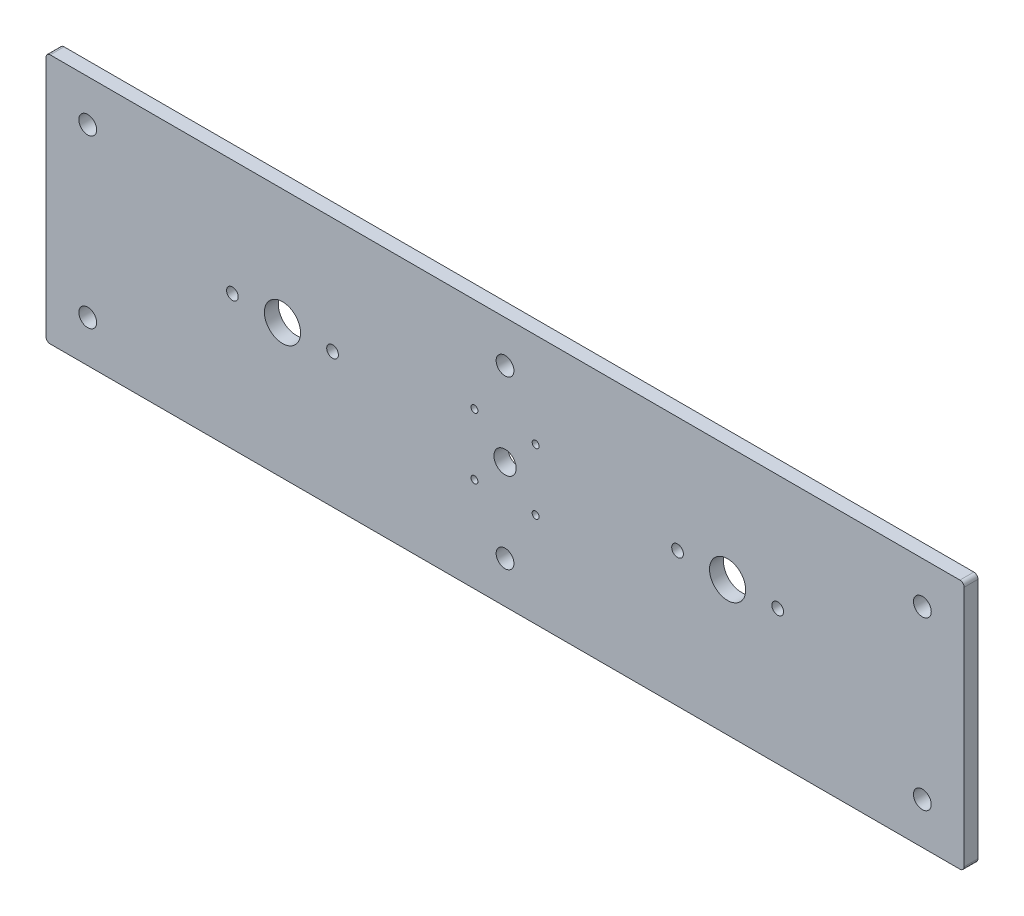
SolidWorks part; units mm, degrees
ref_plane "Front Plane" through (0, 0, 0) normal (0, 0, 1) x (1, 0, 0)
ref_plane "Top Plane" through (0, 0, 0) normal (0, 1, 0) x (1, 0, 0)
ref_plane "Right Plane" through (0, 0, 0) normal (1, 0, 0) x (0, 0, -1)
sketch "Sketch1" plane through (0, 0, 0) normal (0, 0, 1) x (1, 0, 0)
  line L1 (-165, -45) -> (165, -45)
  line L2 (-165, -45) -> (-165, 45)
  line L3 (-165, 45) -> (165, 45)
  line L4 (165, -45) -> (165, 45)
  line L5 (-165, -45) -> (165, 45) construction
  line L6 (-165, 45) -> (165, -45) construction
  point P0 (0, 0)
  dimension "D1" = 330
  dimension "D2" = 90
extrude "Boss-Extrude1" add sketch "Sketch1" along normal mid plane 5
hole_wizard "M6 Clearance Hole1" positions "Sketch6" profile "Sketch5" hole size "M6" standard "ANSI Metric"
sketch "Sketch6" plane through (0, 0, 2.5) normal (0, 0, 1) x (1, 0, 0)
  line L0 (-999.1588, 30) -> (49000.8412, 30) construction
  line L1 (-996.5045, -30) -> (49003.4955, -30) construction
  line L2 (-150, -995.3212) -> (-150, 49004.6788) construction
  line L3 (0, -1000) -> (0, 49000) construction
  line L4 (150, -1006.2702) -> (150, 48993.7298) construction
  line L5 (-165, 45) -> (-165, -45) construction
  line L6 (165, -45) -> (165, 45) construction
  line L7 (165, 45) -> (-165, 45) construction
  line L8 (-165, -45) -> (165, -45) construction
  point P27 (-150, 30)
  point P29 (-150, -30)
  point P31 (0, 30)
  point P33 (0, -30)
  point P35 (150, -30)
  point P37 (150, 30)
  dimension "D1" = 15
  dimension "D2" = 15
  dimension "D3" = 15
  dimension "D4" = 15
sketch "Sketch5" plane through (-150, 30, 2.5) normal (1, 0, 0) x (0, -1, 0)
  line L0 (0, 0) -> (0, 11.9228)
  line L1 (0, 11.9228) -> (3.2, 10)
  line L2 (3.2, 10) -> (3.2, 0)
  line L5 (3.2, 0) -> (0, 0)
  line L10 (0, 11.9228) -> (-3.2, 10) construction
  line L11 (0, -6.35) -> (0, 107.95) construction
  dimension "Hole Dia." = 6.4
  dimension "Hole Depth" = 10
  dimension "Drill Angle" = 118
sketch "Sketch3" plane through (0, 0, 2.5) normal (0, 0, 1) x (1, 0, 0)
  line L0 (-165, 3.4) -> (165, 3.4) construction
  circle A0 centre (-80, 3.4) radius 6.5
  dimension "D1" = 13
  dimension "D7" = 80
  dimension "D3" = 3.4
extrude "Cut-Extrude2" cut sketch "Sketch3" against normal through all
hole_wizard "M5x0.8 Tapped Hole1" positions "Sketch8" profile "Sketch7" tap size "M5x0.8" standard "ANSI Metric" end condition through all
sketch "Sketch8" plane through (0, 0, 2.5) normal (0, 0, 1) x (1, 0, 0)
  line L0 (-1080, 3.4) -> (48920, 3.4) construction
  circle A0 centre (-80, 3.4) radius 6.5 construction
  point P6 (-98, 3.4)
  point P8 (-62, 3.4)
  dimension "D1" = 18
  dimension "D2" = 18
sketch "Sketch7" plane through (-98, 3.4, 2.5) normal (1, 0, 0) x (0, -1, 0)
  line L0 (0, 0) -> (0, 5)
  line L1 (0, 5) -> (2.1, 5)
  line L2 (2.1, 5) -> (2.1, 0)
  line L5 (2.1, 0) -> (0, 0)
  line L11 (0, -6.35) -> (0, 107.95) construction
  dimension "Thru Tap Drill Dia." = 4.2
  dimension "Thru Tap Drill Depth" = 5
cosmetic thread "Hole Thread1" parameters "D2"=5
cosmetic thread "Hole Thread2" parameters "D2"=5
mirror "Mirror1" about plane through (0, 0, 0) normal (1, 0, 0) of "M5x0.8 Tapped Hole1", "Cut-Extrude2"
sketch "Sketch4" plane through (0, 0, 2.5) normal (0, 0, 1) x (1, 0, 0)
  circle A0 centre (0, 0) radius 4
  dimension "D1" = 8
extrude "Cut-Extrude3" cut sketch "Sketch4" against normal through all
hole_wizard "M3x0.5 Tapped Hole1" positions "Sketch10" profile "Sketch9" tap size "M3x0.5" standard "ANSI Metric" end condition through all
sketch "Sketch10" plane through (0, 0, 2.5) normal (0, 0, 1) x (1, 0, 0)
  line L1 (-11, -11) -> (11, -11) construction
  line L2 (-11, -11) -> (-11, 11) construction
  line L3 (-11, 11) -> (11, 11) construction
  line L4 (11, -11) -> (11, 11) construction
  line L5 (-11, -11) -> (11, 11) construction
  line L6 (-11, 11) -> (11, -11) construction
  point P2 (11, 11)
  point P67 (-11, -11)
  point P68 (-11, 11)
  point P69 (11, -11)
  dimension "D1" = 22
  dimension "D2" = 22
  dimension "D3" = 11
  dimension "D4" = 11
sketch "Sketch9" plane through (11, 11, 2.5) normal (1, 0, 0) x (0, -1, 0)
  line L0 (0, 0) -> (0, 5)
  line L1 (0, 5) -> (1.25, 5)
  line L2 (1.25, 5) -> (1.25, 0)
  line L5 (1.25, 0) -> (0, 0)
  line L11 (0, -6.35) -> (0, 107.95) construction
  dimension "Thru Tap Drill Dia." = 2.5
  dimension "Thru Tap Drill Depth" = 5
cosmetic thread "Hole Thread3" parameters "D2"=3
cosmetic thread "Hole Thread4" parameters "D2"=3
cosmetic thread "Hole Thread5" parameters "D2"=3
cosmetic thread "Hole Thread6" parameters "D2"=3
fillet "Fillet1" radius 1.5 4 edges at (-165, -45, 0) (-165, 45, 0) (165, -45, 0) (165, 45, 0)
